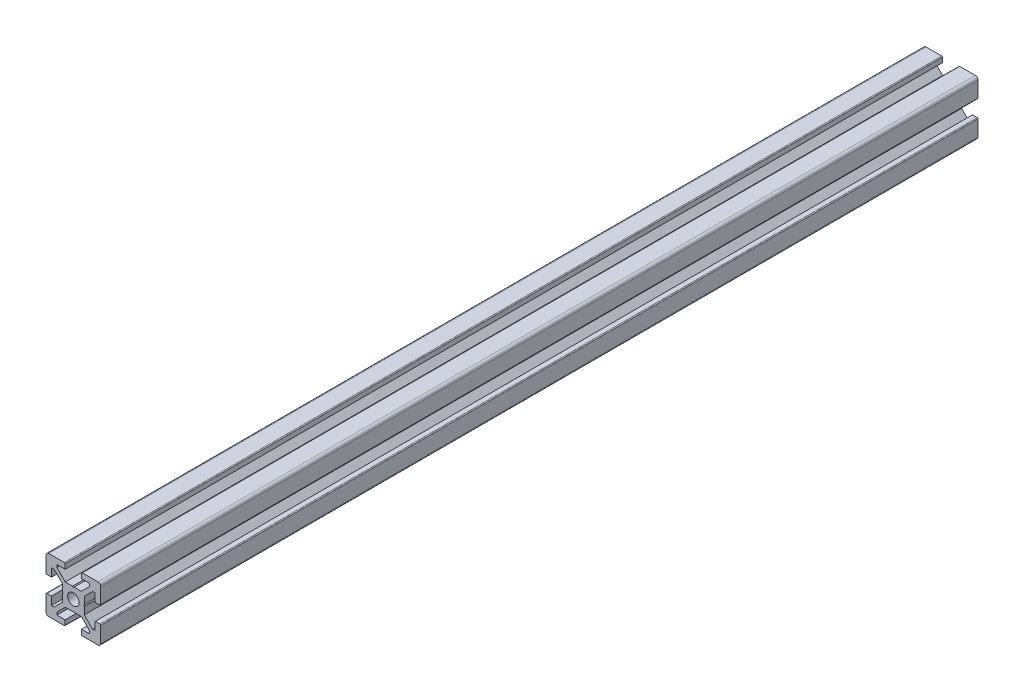
SolidWorks part; units mm, degrees
ref_plane "Front Plane" through (0, 0, 0) normal (0, 0, 1) x (1, 0, 0)
ref_plane "Top Plane" through (0, 0, 0) normal (0, 1, 0) x (1, 0, 0)
ref_plane "Right Plane" through (0, 0, 0) normal (1, 0, 0) x (0, 0, -1)
sketch "Sketch1" plane through (0, 0, 0) normal (0, 0, -1) x (-1, 0, 0)
  line L0 (10, 3.3) -> (10, 9)
  line L1 (9, 10) -> (3.3, 10)
  line L2 (3, 9.7) -> (3, 8)
  line L3 (3, 8) -> (6, 8)
  line L4 (6, 8) -> (6, 7.0607)
  line L5 (6, 7.0607) -> (2.9393, 4)
  line L6 (2.9393, 4) -> (0.3, 4)
  line L7 (0.3, 4) -> (0, 3.7)
  line L8 (0, 3.7) -> (-0.3, 4)
  line L9 (-0.3, 4) -> (-2.9393, 4)
  line L10 (-2.9393, 4) -> (-6, 7.0607)
  line L11 (-6, 7.0607) -> (-6, 8)
  line L12 (-6, 8) -> (-3, 8)
  line L13 (-3, 8) -> (-3, 9.7)
  line L14 (-3.3, 10) -> (-9, 10)
  line L15 (-10, 9) -> (-10, 3.3)
  line L16 (-9.7, 3) -> (-8, 3)
  line L17 (-8, 3) -> (-8, 6)
  line L18 (-8, 6) -> (-7.0607, 6)
  line L19 (-7.0607, 6) -> (-4, 2.9393)
  line L20 (-4, 2.9393) -> (-4, 0.3)
  line L21 (-4, 0.3) -> (-3.7, 0)
  line L22 (-3.7, 0) -> (-4, -0.3)
  line L23 (-4, -0.3) -> (-4, -2.9393)
  line L24 (-4, -2.9393) -> (-7.0607, -6)
  line L25 (-7.0607, -6) -> (-8, -6)
  line L26 (-8, -6) -> (-8, -3)
  line L27 (-8, -3) -> (-9.7, -3)
  line L28 (-10, -3.3) -> (-10, -9)
  line L29 (-9, -10) -> (-3.3, -10)
  line L30 (-3, -9.7) -> (-3, -8)
  line L31 (-3, -8) -> (-6, -8)
  line L32 (-6, -8) -> (-6, -7.0607)
  line L33 (-6, -7.0607) -> (-2.9393, -4)
  line L34 (-2.9393, -4) -> (-0.3, -4)
  line L35 (-0.3, -4) -> (0, -3.7)
  line L36 (0, -3.7) -> (0.3, -4)
  line L37 (0.3, -4) -> (2.9393, -4)
  line L38 (2.9393, -4) -> (6, -7.0607)
  line L39 (6, -7.0607) -> (6, -8)
  line L40 (6, -8) -> (3, -8)
  line L41 (3, -8) -> (3, -9.7)
  line L42 (3.3, -10) -> (9, -10)
  line L43 (10, -9) -> (10, -3.3)
  line L44 (9.7, -3) -> (8, -3)
  line L45 (8, -3) -> (8, -6)
  line L46 (8, -6) -> (7.0607, -6)
  line L47 (7.0607, -6) -> (4, -2.9393)
  line L48 (4, -2.9393) -> (4, -0.3)
  line L49 (4, -0.3) -> (3.7, 0)
  line L50 (3.7, 0) -> (4, 0.3)
  line L51 (4, 0.3) -> (4, 2.9393)
  line L52 (4, 2.9393) -> (7.0607, 6)
  line L53 (7.0607, 6) -> (8, 6)
  line L54 (8, 6) -> (8, 3)
  line L55 (8, 3) -> (9.7, 3)
  line L56 (9, -9) -> (-9, 9) construction
  line L57 (-9, -9) -> (9, 9) construction
  line L58 (-3.7, 0) -> (3.7, 0) construction
  line L59 (0, -3.7) -> (0, 3.7) construction
  circle A0 centre (0, 0) radius 2.1
  arc A1 (10, 9) -> (9, 10) centre (9, 9) ccw
  arc A2 (3.3, 10) -> (3, 9.7) centre (3.3, 9.7) ccw
  arc A3 (-3, 9.7) -> (-3.3, 10) centre (-3.3, 9.7) ccw
  arc A4 (-9, 10) -> (-10, 9) centre (-9, 9) ccw
  arc A5 (-10, 3.3) -> (-9.7, 3) centre (-9.7, 3.3) ccw
  arc A6 (-9.7, -3) -> (-10, -3.3) centre (-9.7, -3.3) ccw
  arc A7 (-10, -9) -> (-9, -10) centre (-9, -9) ccw
  arc A8 (-3.3, -10) -> (-3, -9.7) centre (-3.3, -9.7) ccw
  arc A9 (3, -9.7) -> (3.3, -10) centre (3.3, -9.7) ccw
  arc A10 (9, -10) -> (10, -9) centre (9, -9) ccw
  arc A11 (10, -3.3) -> (9.7, -3) centre (9.7, -3.3) ccw
  arc A12 (9.7, 3) -> (10, 3.3) centre (9.7, 3.3) ccw
  point P83 (0, 0)
  point P85 (0, 0)
  point P86 (0, 0)
  dimension "D1" = 1
  dimension "D4" = 0.3
  dimension "D10" = 4.2
  dimension "D2" = 20
  dimension "D3" = 6
  dimension "D5" = 3
  dimension "D6" = 1.7
  dimension "D7" = 0.9393
  dimension "D8" = 0.6
  dimension "D9" = 4
  dimension "D11" = 3.0607
  dimension "D12" = 3.0607
  dimension "D13" = 3.0607
  dimension "D14" = 5.7
  dimension "D15" = 5.7
  dimension "D16" = 0.9393
  dimension "D17" = 0.9393
  dimension "D18" = 3.0607
extrude "Boss-Extrude1" add sketch "Sketch1" against normal mid plane 320.9
ref_axis "Axis1" through (0, 0, 160.45) along (0, 0, -1)
